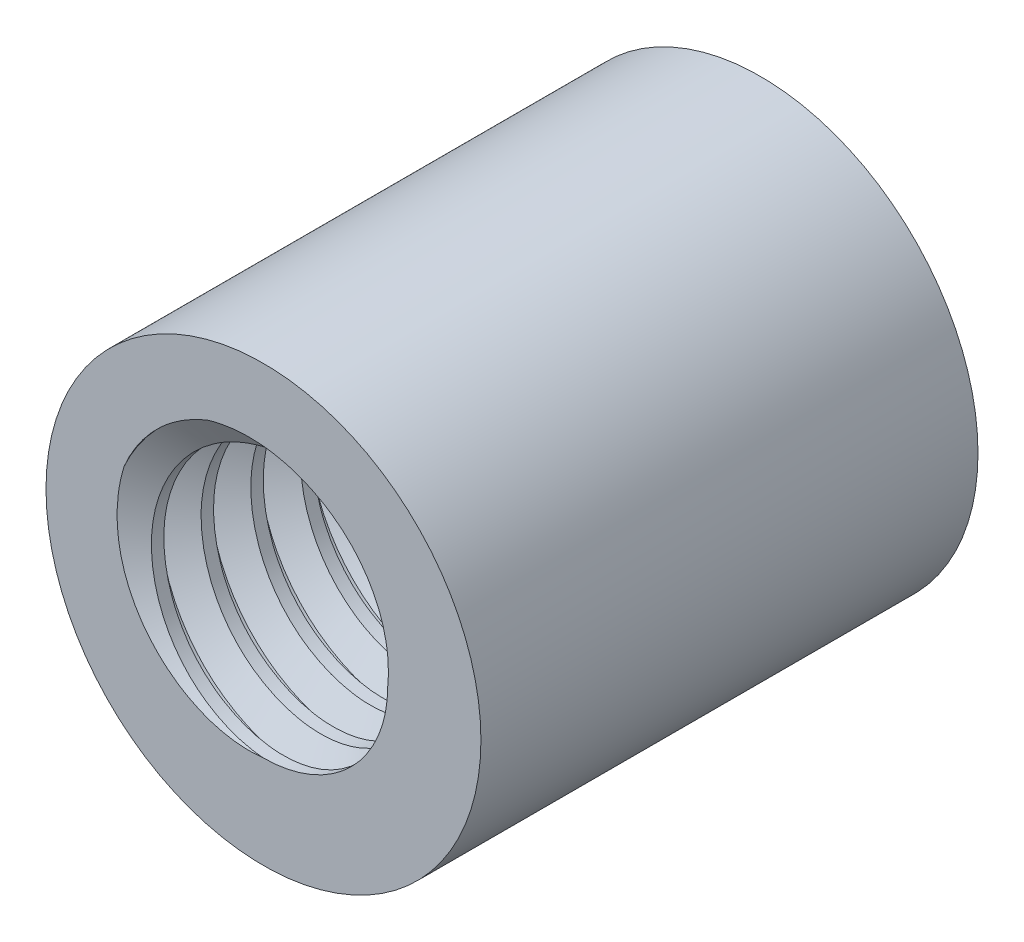
SolidWorks part; units mm, degrees
material "Brass"
ref_plane "Front Plane" through (0, 0, 0) normal (0, 0, 1) x (1, 0, 0)
ref_plane "Top Plane" through (0, 0, 0) normal (0, 1, 0) x (1, 0, 0)
ref_plane "Right Plane" through (0, 0, 0) normal (1, 0, 0) x (0, 0, -1)
sketch "Sketch1" plane through (0, 0, 0) normal (0, 0, 1) x (1, 0, 0)
  circle A0 centre (0, 0) radius 1.75
  circle A1 centre (0, 0) radius 1
  dimension "D1" = 3.5
  dimension "D2" = 2
extrude "Boss-Extrude1" add sketch "Sketch1" along normal blind 4
thread "Thread2" pitch 0.4 method cut trim with start face yes trim with end face yes profile "Thread Profile2" start angle 0, offset 1, length 10, pitch 0.4, diameter 2
ref_plane "Plane2" through (-1, 0, 5) normal (0, -1, 0) x (-1, 0, 0)
sketch "Thread Profile2" plane through (-1, 0, 5) normal (0, -1, 0) x (-1, 0, 0)
  line L0 (0, 0) -> (0, 0.4) construction
  line L1 (0, 0) -> (0.2165, 0.125)
  line L2 (0.2165, 0.125) -> (0.2165, 0.175)
  line L3 (0.2165, 0.175) -> (0, 0.3)
  line L4 (0.2165, 0.15) -> (0, 0.15) construction
  line L11 (0, 0) -> (0, 0.3)
  point P2 (0, 0)
  dimension "Pitch" = 0.4
  dimension "Profile_Angle" = 60
  dimension "Profile_Land" = 0.05
  dimension "Profile_Height" = 0.2165
